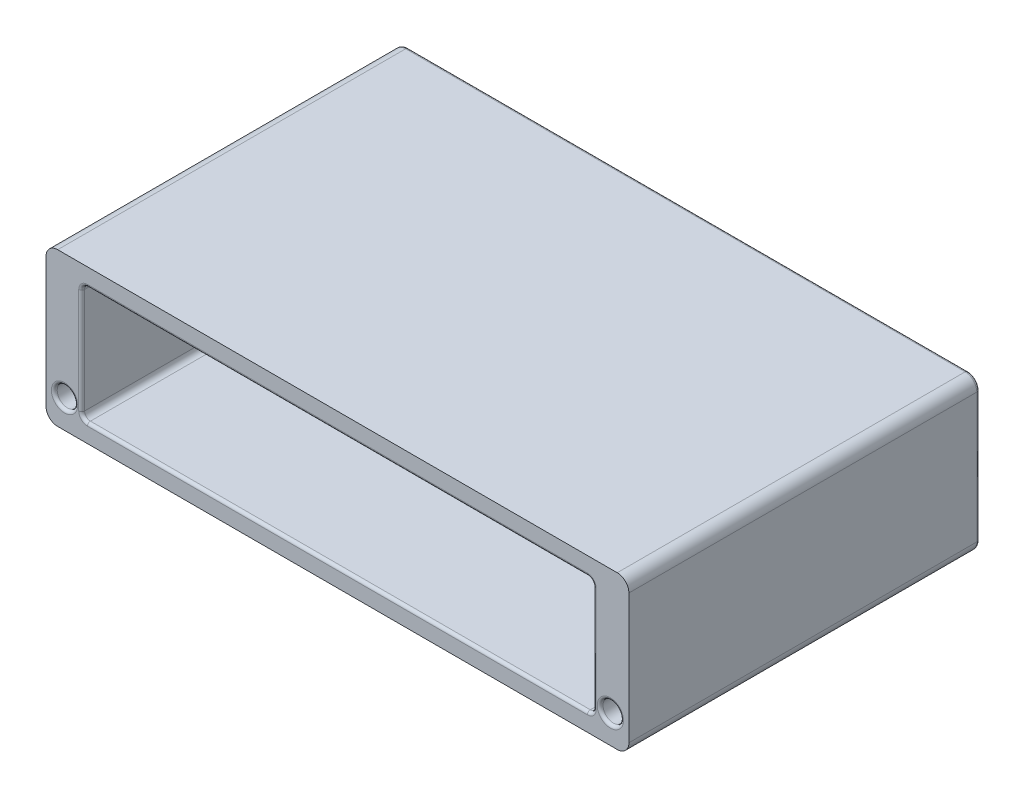
SolidWorks part; units mm, degrees
ref_plane "前视基准面" through (0, 0, 0) normal (0, 0, 1) x (1, 0, 0)
ref_plane "上视基准面" through (0, 0, 0) normal (0, 1, 0) x (1, 0, 0)
ref_plane "右视基准面" through (0, 0, 0) normal (1, 0, 0) x (0, 0, -1)
sketch "草图2" plane through (0, 0, 0) normal (0, 0, 1) x (1, 0, 0)
  line L0 (-175, 0) -> (-199.3912, 0) construction
  line L1 (199.3912, -52.3751) -> (-199.3912, -52.3751)
  line L2 (199.3912, -52.3751) -> (199.3912, 52.3751)
  line L3 (199.3912, 52.3751) -> (-199.3912, 52.3751)
  line L4 (-199.3912, -52.3751) -> (-199.3912, 52.3751)
  line L5 (199.3912, -52.3751) -> (-199.3912, 52.3751) construction
  line L6 (199.3912, 52.3751) -> (-199.3912, -52.3751) construction
  line L11 (152.2794, -40) -> (-152.2794, 40) construction
  line L12 (152.2794, 40) -> (-152.2794, -40) construction
  line L13 (175, -40) -> (-175, -40)
  line L14 (175, -40) -> (175, 40)
  line L15 (175, 40) -> (-175, 40)
  line L16 (-175, -40) -> (-175, 40)
  line L17 (175, -40) -> (-175, 40) construction
  line L18 (175, 40) -> (-175, -40) construction
  line L19 (175, 0) -> (199.3912, 0) construction
  line L20 (0, 52.3751) -> (0, -52.3751) construction
  circle A1 centre (-186.7171, -33.023) radius 7
  circle A2 centre (186.7171, -33.023) radius 7
  point P0 (0, 0)
  point P5 (0, 0)
  point P11 (0, 0)
  point P26 (-186.7354, 33.996)
  point P27 (-186.8253, 26.4078)
  point P28 (-187.1956, 0)
  point P29 (0, 0)
  point P30 (0, 0)
  point P31 (-186.4343, -26.7207)
  point P36 (-187.1669, 32.0543)
  point P37 (-185.8584, -30.5388)
  point P38 (-186.7171, -33.023)
extrude "凸台-拉伸2" add sketch "草图2" along normal blind 240
sketch "草图7" plane through (0, 0, 0) normal (0, 0, -1) x (-1, 0, 0)
  line L0 (199.3912, -52.3751) -> (-199.3912, -52.3751) construction
  line L1 (-175, -40) -> (175, -40)
  line L2 (-175, -40) -> (-175, -52.3751)
  line L3 (-175, -52.3751) -> (175, -52.3751)
  line L4 (175, -40) -> (175, -52.3751)
extrude "切除-拉伸2" cut sketch "草图7" against normal blind 25
fillet "圆角2" radius 4 4 edges at (-175, -40, 132.5) (-175, 40, 120) (175, -40, 132.5) (175, 40, 120)
fillet "圆角8" radius 8 4 edges at (-199.3912, 52.3751, 120) (-199.3912, -52.3751, 120) (199.3912, -52.3751, 120) (199.3912, 52.3751, 120)
fillet "圆角3" radius 2 14 edges at (-175, -8.1875, 0) (-173.8284, 38.8284, 0) (0, 40, 0) (173.8284, 38.8284, 0) (199.3912, 0, 0) (-199.3912, 0, 0) (175, -8.1875, 0) (0, 52.3751, 0) (197.0481, 50.0319, 0) (197.0481, -50.0319, 0) (-197.0481, -50.0319, 0) (-197.0481, 50.0319, 0) (183.1956, -52.3751, 0) (-183.1956, -52.3751, 0)
fillet "圆角5" radius 2 8 edges at (-175, 0, 240) (-173.8284, -38.8284, 240) (175, 0, 240) (173.8284, -38.8284, 240) (0, -40, 240) (-173.8284, 38.8284, 240) (0, 40, 240) (173.8284, 38.8284, 240)
fillet "圆角7" radius 2 4 edges at (179.7171, -33.023, 240) (-179.7171, -33.023, 240) (-179.7171, -33.023, 0) (179.7171, -33.023, 0)
sketch "草图5" plane through (0, 0, 240) normal (0, 0, 1) x (1, 0, 0)
  line L0 (-186.7171, -33.023) -> (186.7171, -33.023) construction
  point P4 (0, 0)
fillet "圆角9" radius 2 8 edges at (-175.5858, -51.7893, 0.5858) (175.5858, -51.7893, 0.5858) (-173.8284, -38.8284, 25) (173.8284, -38.8284, 25) (-175, -52.3751, 13.5) (175, -52.3751, 13.5) (0, -52.3751, 25) (0, -40, 25)
